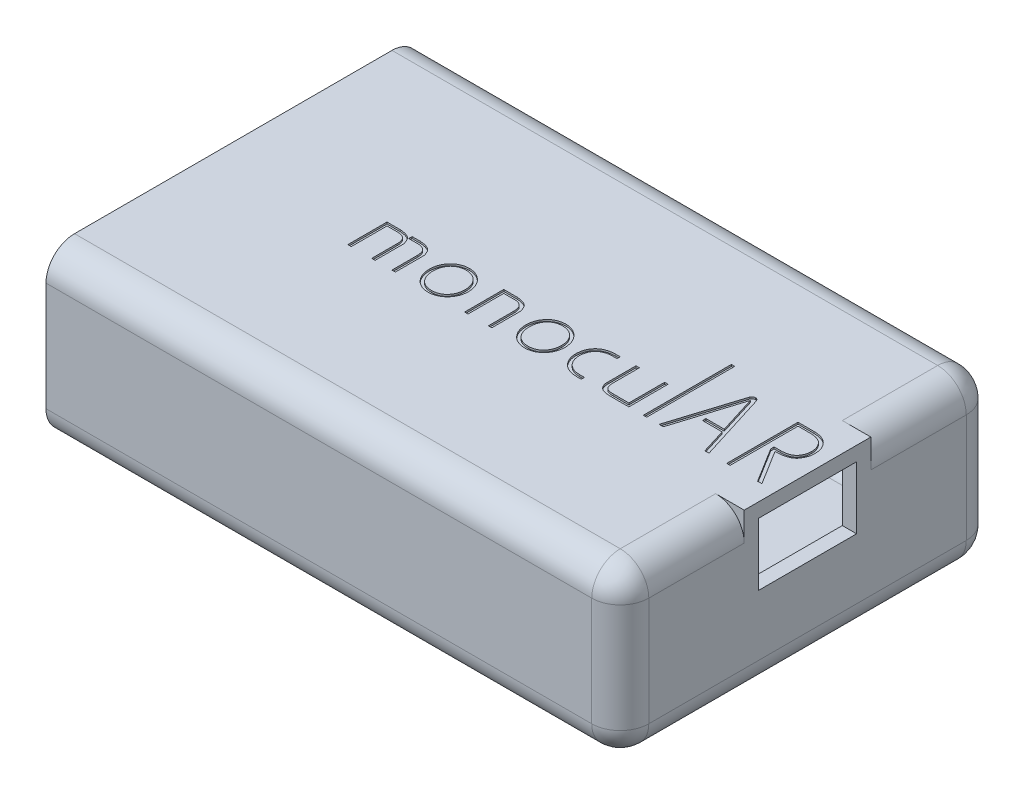
SolidWorks part; units mm, degrees
ref_plane "Front Plane" through (0, 0, 0) normal (0, 0, 1) x (1, 0, 0)
ref_plane "Top Plane" through (0, 0, 0) normal (0, 1, 0) x (1, 0, 0)
ref_plane "Right Plane" through (0, 0, 0) normal (1, 0, 0) x (0, 0, -1)
sketch "Sketch1" plane through (0, 0, 0) normal (0, 1, 0) x (1, 0, 0)
  line L0 (-32, 21) -> (32, 21)
  line L1 (-30, -19) -> (30, -19) construction
  line L2 (-30, -19) -> (-30, 19) construction
  line L3 (-30, 19) -> (30, 19) construction
  line L4 (30, -19) -> (30, 19) construction
  line L5 (-30, -19) -> (30, 19) construction
  line L6 (-30, 19) -> (30, -19) construction
  line L7 (32, -21) -> (32, 21)
  line L8 (-32, -21) -> (32, -21)
  line L9 (-32, -21) -> (-32, 21)
  point P0 (0, 0)
  point P6 (0, 0)
  dimension "D1" = 38
  dimension "D2" = 60
  dimension "D3" = 2
extrude "Boss-Extrude1" add sketch "Sketch1" along normal blind 1.6
sketch "Sketch2" plane through (0, 1.6, 0) normal (0, 1, 0) x (1, 0, 0)
  line L0 (-30.4, 19.4) -> (-30.4, -19.4)
  line L1 (-30.4, -19.4) -> (30.4, -19.4)
  line L2 (30.4, -19.4) -> (30.4, 19.4)
  line L3 (30.4, 19.4) -> (-30.4, 19.4)
  line L4 (-32, 21) -> (-32, -21)
  line L5 (-32, -21) -> (32, -21)
  line L6 (32, -21) -> (32, 21)
  line L7 (32, 21) -> (-32, 21)
  line L8 (-32, 21) -> (-32, -21)
  line L9 (-32, -21) -> (32, -21)
  line L10 (32, -21) -> (32, 21)
  line L11 (32, 21) -> (-32, 21)
  dimension "D1" = 0
  dimension "D2" = 1.6
extrude "Boss-Extrude2" add sketch "Sketch2" along normal blind 17
sketch "Sketch3" plane through (0, 1.6, 0) normal (0, 1, 0) x (1, 0, 0)
  line L0 (30.4, -19.4) -> (30.4, 19.4) construction
  line L1 (-30.4, 19.4) -> (30.4, 19.4)
  line L2 (-30.4, 19.4) -> (-30.4, 14.4)
  line L3 (-30.4, 14.4) -> (30.4, 14.4)
  line L4 (30.4, 19.4) -> (30.4, 14.4)
  line L6 (-30.4, -19.4) -> (30.4, -19.4)
  line L7 (-30.4, -19.4) -> (-30.4, -14.4)
  line L8 (-30.4, -14.4) -> (30.4, -14.4)
  line L9 (30.4, -19.4) -> (30.4, -14.4)
  dimension "D1" = 5
extrude "Boss-Extrude3" add sketch "Sketch3" along normal blind 5
sketch "Sketch4" plane through (32, 0, 0) normal (1, 0, 0) x (0, 0, -1)
  line L1 (0, 0) -> (0, 18.6) construction
  line L2 (-21, 0) -> (21, 0) construction
  line L3 (-21, 18.6) -> (21, 18.6) construction
  line L5 (-5.5, 10) -> (5.5, 10)
  line L6 (-5.5, 10) -> (-5.5, 18)
  line L7 (-5.5, 18) -> (5.5, 18)
  line L8 (5.5, 10) -> (5.5, 18)
  line L9 (-5.5, 10) -> (5.5, 18) construction
  line L10 (-5.5, 18) -> (5.5, 10) construction
  point P4 (0, 14)
  dimension "D1" = 14
  dimension "D2" = 8
  dimension "D3" = 11
extrude "Cut-Extrude1" cut sketch "Sketch4" against normal blind 5
sketch "Sketch5" plane through (-32, 0, 0) normal (-1, 0, 0) x (0, 0, 1)
  line L1 (-21, 0) -> (21, 0) construction
  line L2 (0, 12) -> (0, 0) construction
  circle A0 centre (0, 12) radius 2
  dimension "D1" = 4
  dimension "D2" = 12
extrude "Cut-Extrude2" cut sketch "Sketch5" against normal blind 5
sketch "Sketch7" plane through (0, 6.6, 0) normal (0, 1, 0) x (1, 0, 0)
  line L0 (-26.4, 14.4) -> (-21.4, 19.4)
  line L1 (-30.4, 14.4) -> (30.4, 14.4) construction
  line L2 (30.4, 19.4) -> (-30.4, 19.4) construction
  line L3 (-21.4, 19.4) -> (21.4, 19.4)
  line L4 (21.4, 19.4) -> (26.4, 14.4)
  line L5 (-30.4, 14.4) -> (30.4, 14.4) construction
  line L6 (26.4, 14.4) -> (-26.4, 14.4)
  line L7 (-30.4, 19.4) -> (-30.4, -19.4) construction
  line L8 (30.4, 14.4) -> (30.4, 19.4) construction
  line L9 (-30.4, 0) -> (30.4, 0) construction
  line L10 (30.4, -19.4) -> (30.4, 19.4) construction
  line L11 (21.4, -19.4) -> (26.4, -14.4)
  line L12 (26.4, -14.4) -> (-26.4, -14.4)
  line L13 (-26.4, -14.4) -> (-21.4, -19.4)
  line L14 (-21.4, -19.4) -> (21.4, -19.4)
  dimension "D1" = 4
  dimension "D2" = 45
  dimension "D3" = 45
  dimension "D4" = 4
extrude "Cut-Extrude3" cut sketch "Sketch7" against normal blind 5
pattern_linear "LPattern1" count 2 spacing 7 along (0, 1, 0) of "Cut-Extrude3", "Boss-Extrude3"
sketch "Sketch6" plane through (0, 18.6, 0) normal (0, 1, 0) x (1, 0, 0)
  line L5 (-30.4, 19.4) -> (-30.4, -19.4)
  line L6 (30.4, 19.4) -> (-30.4, 19.4)
  line L7 (30.4, -19.4) -> (30.4, 19.4)
  line L8 (-30.4, -19.4) -> (30.4, -19.4)
  line L9 (-30.4, 19.4) -> (-30.4, -19.4)
  line L10 (30.4, 19.4) -> (-30.4, 19.4)
  line L11 (30.4, -19.4) -> (30.4, 19.4)
  line L12 (-30.4, -19.4) -> (30.4, -19.4)
  dimension "D1" = 0
extrude "Boss-Extrude4" add sketch "Sketch6" against normal blind 1.6
sketch "Sketch17" plane through (0, 0, -14.4) normal (0, 0, 1) x (1, 0, 0)
  line L0 (-21.4, 8.6) -> (-21.4, 13.6) construction
  line L1 (-30.4, 13.6) -> (-21.4, 13.6)
  line L2 (-30.4, 13.6) -> (-30.4, 10.2)
  line L3 (-30.4, 10.2) -> (-21.4, 10.2)
  line L4 (-21.4, 13.6) -> (-21.4, 10.2)
  line L5 (30.4, 13.6) -> (30.4, 8.6) construction
  line L6 (21.4, 13.6) -> (30.4, 13.6)
  line L7 (21.4, 13.6) -> (21.4, 10.2)
  line L8 (21.4, 10.2) -> (30.4, 10.2)
  line L9 (30.4, 13.6) -> (30.4, 10.2)
  line L11 (-21.4, 5) -> (-30.4, 5)
  line L12 (-21.4, 5) -> (-21.4, 1.6)
  line L13 (-21.4, 1.6) -> (-30.4, 1.6)
  line L14 (-30.4, 5) -> (-30.4, 1.6)
  line L15 (30.4, 6.6) -> (30.4, 1.6) construction
  line L16 (21.4, 5) -> (30.4, 5)
  line L17 (21.4, 5) -> (21.4, 1.6)
  line L18 (21.4, 1.6) -> (30.4, 1.6)
  line L19 (30.4, 5) -> (30.4, 1.6)
  line L21 (-21.4, 1.6) -> (-26.4, 1.6) construction
  line L22 (-21.4, 1.6) -> (-21.4, 6.6) construction
  line L23 (21.4, 1.6) -> (21.4, 6.6) construction
  line L24 (30.4, 1.6) -> (26.4, 1.6) construction
  dimension "D1" = 1.6
extrude "Cut-Extrude8" cut sketch "Sketch17" against normal up to surface and the other way up to surface up to face at (0, 9.525, -19.4) other way up to face at (0, 9.525, 19.4)
fillet "Fillet1" radius 1.6 13 edges at (30.4, 7.6, -19.4) (30.4, 3.3, -19.4) (0, 1.6, -19.4) (0, 1.6, 19.4) (30.4, 13.6, -19.4) (30.4, 1.6, 0) (30.4, 3.3, 19.4) (30.4, 7.6, 19.4) (30.4, 13.6, 19.4) (0, 17, 19.4) (0, 17, -19.4) (30.4, 17, -12.45) (30.4, 17, 12.45)
fillet "Fillet2" radius 3.2 8 edges at (0, 18.6, -21) (0, 0, -21) (0, 0, 21) (0, 18.6, 21) (32, 9.3, 21) (32, 0, 0) (32, 9.3, -21) (32, 18.6, 0)
sketch "Sketch18" plane through (32, 0, 0) normal (1, 0, 0) x (0, 0, -1)
  line L0 (-5.5, 15.4) -> (-17.8, 15.4) construction
  line L1 (-7.1, 15.4) -> (-5.5, 15.4)
  line L2 (-7.1, 15.4) -> (-7.1, 18.6)
  line L3 (-7.1, 18.6) -> (7.1, 18.6)
  line L4 (7.1, 15.4) -> (7.1, 18.6)
  line L5 (-17.8, 18.6) -> (17.8, 18.6) construction
  line L6 (-5.5, 15.4) -> (-5.5, 17)
  line L7 (-5.5, 17) -> (5.5, 17)
  line L8 (5.5, 17) -> (5.5, 15.4)
  line L9 (5.5, 15.4) -> (7.1, 15.4)
  dimension "D1" = 1.6
  dimension "D2" = 1.6
extrude "Boss-Extrude5" add sketch "Sketch18" against normal up to surface up to face at (31.1106, 17.056, 0)
sketch "Sketch19" plane through (0, 18.6, 0) normal (0, 1, 0) x (1, 0, 0)
  line L1 (-25.6895, -3.55) -> (-11.5969, -3.55) construction
  line L2 (28.8, -7.1) -> (32, -7.1) construction
  text T0 "monoculAR" font "rosie" height 8
  dimension "D1" = 3.55
extrude "Cut-Extrude9" cut sketch "Sketch19" against normal blind 0.2
sketch "Sketch20" plane through (-32, 0, 0) normal (-1, 0, 0) x (0, 0, 1)
  line L4 (17.8, 18.6) -> (-17.8, 18.6)
  line L5 (-21, 15.4) -> (-21, 3.2)
  line L6 (-17.8, 0) -> (17.8, 0)
  line L7 (21, 3.2) -> (21, 15.4)
  line L8 (17.8, 18.6) -> (-17.8, 18.6)
  line L9 (-21, 15.4) -> (-21, 3.2)
  line L10 (-17.8, 0) -> (17.8, 0)
  line L11 (21, 3.2) -> (21, 15.4)
  arc A4 (-17.8, 18.6) -> (-21, 15.4) centre (-17.8, 15.4) ccw
  arc A5 (-21, 3.2) -> (-17.8, 0) centre (-17.8, 3.2) ccw
  arc A6 (17.8, 0) -> (21, 3.2) centre (17.8, 3.2) ccw
  arc A7 (21, 15.4) -> (17.8, 18.6) centre (17.8, 15.4) ccw
  arc A8 (-17.8, 18.6) -> (-21, 15.4) centre (-17.8, 15.4) ccw
  arc A9 (-21, 3.2) -> (-17.8, 0) centre (-17.8, 3.2) ccw
  arc A10 (17.8, 0) -> (21, 3.2) centre (17.8, 3.2) ccw
  arc A11 (21, 15.4) -> (17.8, 18.6) centre (17.8, 15.4) ccw
  dimension "D1" = 0
extrude "Cut-Extrude10" cut sketch "Sketch20" against normal blind 1.6
sketch "Sketch21" plane through (-30.4, 0, 0) normal (-1, 0, 0) x (0, 0, 1)
  line L0 (17.8, 17) -> (-17.8, 17)
  line L1 (-19.4, 15.4) -> (-19.4, 3.2)
  line L8 (-17.8, 1.6) -> (17.8, 1.6)
  line L9 (19.4, 3.2) -> (19.4, 15.4)
  line L10 (17.8, 18.6) -> (-17.8, 18.6)
  line L11 (-21, 15.4) -> (-21, 3.2)
  line L12 (-17.8, 0) -> (17.8, 0)
  line L13 (21, 3.2) -> (21, 15.4)
  line L14 (17.8, 18.6) -> (-17.8, 18.6)
  line L16 (-21, 15.4) -> (-21, 3.2)
  line L17 (-17.8, 0) -> (17.8, 0)
  line L18 (21, 3.2) -> (21, 15.4)
  arc A0 (-17.8, 17) -> (-19.4, 15.4) centre (-17.8, 15.4) ccw
  arc A1 (-19.4, 3.2) -> (-17.8, 1.6) centre (-17.8, 3.2) ccw
  arc A2 (17.8, 1.6) -> (19.4, 3.2) centre (17.8, 3.2) ccw
  arc A3 (19.4, 15.4) -> (17.8, 17) centre (17.8, 15.4) ccw
  arc A12 (21, 15.4) -> (17.8, 18.6) centre (17.8, 15.4) ccw
  arc A13 (-17.8, 18.6) -> (-21, 15.4) centre (-17.8, 15.4) ccw
  arc A14 (-21, 3.2) -> (-17.8, 0) centre (-17.8, 3.2) ccw
  arc A15 (17.8, 0) -> (21, 3.2) centre (17.8, 3.2) ccw
  arc A16 (21, 15.4) -> (17.8, 18.6) centre (17.8, 15.4) ccw
  arc A17 (-17.8, 18.6) -> (-21, 15.4) centre (-17.8, 15.4) ccw
  arc A18 (-21, 3.2) -> (-17.8, 0) centre (-17.8, 3.2) ccw
  arc A19 (17.8, 0) -> (21, 3.2) centre (17.8, 3.2) ccw
  arc M9 (21, 15.4) -> (17.8, 18.6) centre (17.8, 15.4) ccw
  line M10 (17.8, 18.6) -> (-17.8, 18.6)
  arc M11 (-17.8, 18.6) -> (-21, 15.4) centre (-17.8, 15.4) ccw
  line M12 (-21, 15.4) -> (-21, 3.2)
  arc M13 (-21, 3.2) -> (-17.8, 0) centre (-17.8, 3.2) ccw
  line M14 (-17.8, 0) -> (17.8, 0)
  arc M15 (17.8, 0) -> (21, 3.2) centre (17.8, 3.2) ccw
  line M16 (21, 3.2) -> (21, 15.4)
  arc M17 (19.4, 3.2) -> (17.8, 1.6) centre (17.8, 3.2) cw
  line M18 (17.8, 1.6) -> (-17.8, 1.6)
  arc M19 (-17.8, 1.6) -> (-19.4, 3.2) centre (-17.8, 3.2) cw
  line M20 (-19.4, 3.2) -> (-19.4, 5)
  line M24 (-19.4, 6.6) -> (-19.4, 8.6)
  line M28 (-19.4, 10.2) -> (-19.4, 15.4)
  line M32 (19.4, 15.4) -> (19.4, 10.2)
  line M36 (19.4, 8.6) -> (19.4, 6.6)
  line M40 (19.4, 5) -> (19.4, 3.2)
  dimension "D1" = 0
  dimension "D2" = 1.6
extrude "Boss-Extrude6" add sketch "Sketch21" along normal blind 2 contours A1 M16 M9 M10 M11 M12 M13 M14 M15 M32 M36 M40 M17 M18 M19 M20 M24 M28 region at (-30.4, 17.3379, 19.7379)
